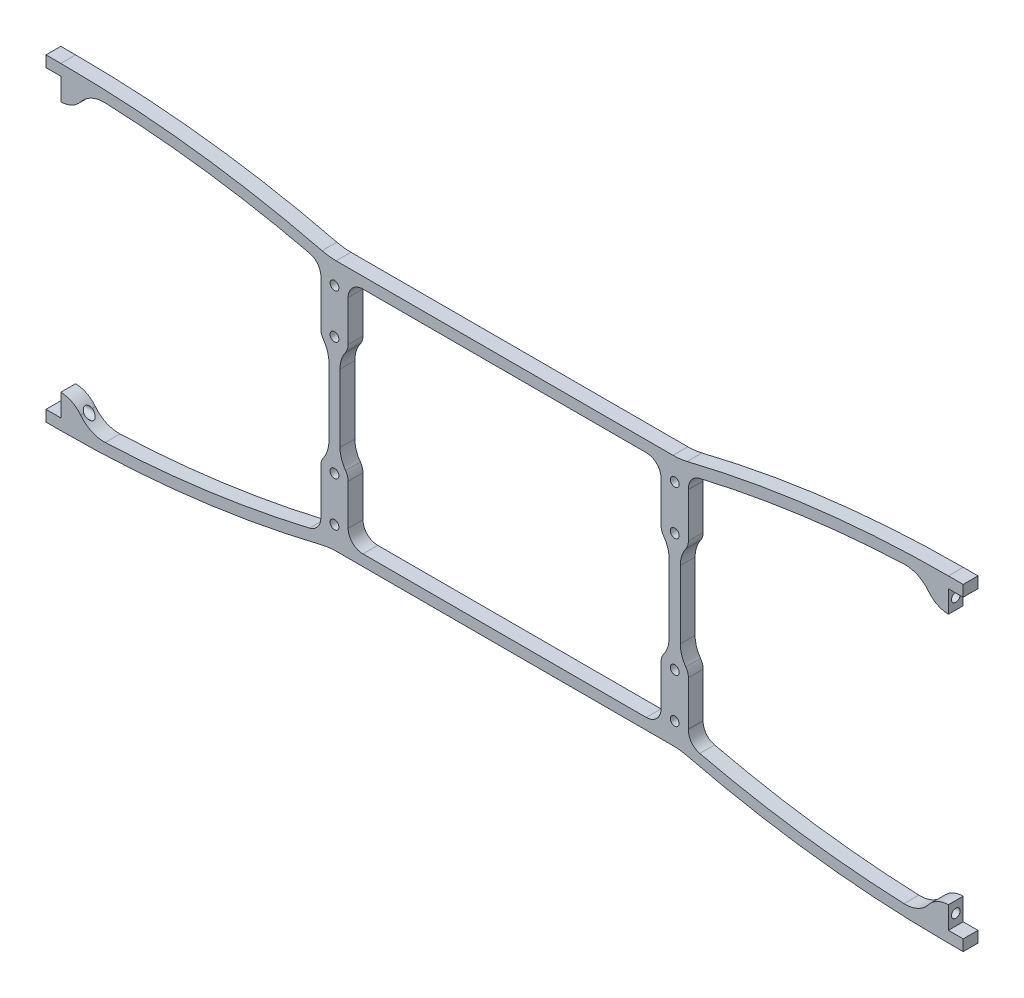
SolidWorks part; units mm, degrees
material "6061-T6 (SS)"
ref_plane "Front Plane" through (0, 0, 0) normal (0, 0, 1) x (1, 0, 0)
ref_plane "Top Plane" through (0, 0, 0) normal (0, 1, 0) x (1, 0, 0)
ref_plane "Right Plane" through (0, 0, 0) normal (1, 0, 0) x (0, 0, -1)
sketch "Sketch1" plane through (0, 0, 0) normal (0, 0, 1) x (1, 0, 0)
  line L0 (0, 49.2125) -> (0, -49.2125) construction
  line L2 (-70.6437, 0) -> (70.6437, 0) construction
  line L3 (70.6437, -49.2125) -> (-70.6437, -49.2125)
  line L4 (70.6437, -49.2125) -> (70.6437, 49.2125)
  line L5 (70.6437, 49.2125) -> (-70.6437, 49.2125)
  line L6 (-70.6437, -49.2125) -> (-70.6437, 49.2125)
  line L8 (-196.85, 65.8813) -> (-190.5, 65.8812) construction
  line L9 (-196.85, 68.2625) -> (-190.5, 68.2625)
  line L10 (75.4063, -53.975) -> (-75.4062, -53.975)
  line L11 (75.4063, -53.975) -> (75.4063, 53.975)
  line L12 (75.4063, 53.975) -> (-75.4062, 53.975)
  line L13 (-75.4062, -53.975) -> (-75.4062, 53.975)
  line L14 (-196.85, 63.5) -> (-190.5, 63.5)
  line L15 (-196.85, 63.5) -> (-196.85, 68.2625)
  line L16 (-190.5, 68.2625) -> (-190.5, 63.5)
  line L17 (-196.85, -65.8813) -> (-190.5, -65.8813) construction
  line L18 (-190.5, -68.2625) -> (-190.5, -63.5)
  line L19 (-196.85, -63.5) -> (-196.85, -68.2625)
  line L20 (-196.85, -63.5) -> (-190.5, -63.5)
  line L21 (-196.85, -68.2625) -> (-190.5, -68.2625)
  line L22 (196.85, -65.8812) -> (190.5, -65.8812) construction
  line L23 (196.85, 65.8813) -> (190.5, 65.8813) construction
  line L24 (196.85, -68.2625) -> (190.5, -68.2625)
  line L25 (196.85, -63.5) -> (190.5, -63.5)
  line L26 (196.85, -63.5) -> (196.85, -68.2625)
  line L27 (190.5, -68.2625) -> (190.5, -63.5)
  line L28 (190.5, 68.2625) -> (190.5, 63.5)
  line L29 (196.85, 63.5) -> (196.85, 68.2625)
  line L30 (196.85, 63.5) -> (190.5, 63.5)
  line L31 (196.85, 68.2625) -> (190.5, 68.2625)
  line L32 (-73.025, -53.975) -> (-73.025, 53.975) construction
  arc A0 (-27.6178, 36.6442) -> (-190.5, 65.8812) centre (-190.5, -402.4533) ccw construction
  arc A1 (-75.4062, 53.975) -> (-190.5, 68.2625) centre (-190.5, -402.4533) ccw
  arc A2 (-75.4062, 49.0618) -> (-190.5, 63.5) centre (-190.5, -402.4533) ccw
  arc A3 (34.7381, 10.8761) -> (-190.5, 68.2625) centre (-190.5, -402.4533) ccw construction
  arc A4 (32.4592, 6.6942) -> (-190.5, 63.5) centre (-190.5, -402.4533) ccw construction
  arc A5 (33.5986, 8.7851) -> (-190.5, 65.8812) centre (-190.5, -402.4533) ccw construction
  arc A6 (-75.4062, -49.0618) -> (-190.5, -63.5) centre (-190.5, 402.4533) cw
  arc A7 (-75.4062, -53.975) -> (-190.5, -68.2625) centre (-190.5, 402.4533) cw
  arc A8 (75.4062, -53.975) -> (190.5, -68.2625) centre (190.5, 402.4533) ccw
  arc A9 (75.4062, -49.0618) -> (190.5, -63.5) centre (190.5, 402.4533) ccw
  arc A10 (75.4062, 49.0618) -> (190.5, 63.5) centre (190.5, -402.4533) cw
  arc A11 (75.4062, 53.975) -> (190.5, 68.2625) centre (190.5, -402.4533) cw
  point P1 (0, 0)
  point P9 (0, 0)
  dimension "D1" = 4.7625
  dimension "D2" = 4.7625
  dimension "D5" = 6.35
  dimension "D3" = 107.95
  dimension "D7" = 131.7625
  dimension "D8" = 2.3813
  dimension "D6" = 381
  dimension "D4" = 146.05
  dimension "D10" = 0
  dimension "D9" = 2.3813
extrude "Boss-Extrude1" add sketch "Sketch1" along normal blind 6.35
sketch "Sketch2" plane through (0, 0, 6.35) normal (0, 0, 1) x (1, 0, 0)
  line L1 (-190.5, 65.8812) -> (-184.15, 65.8813)
  line L2 (-190.5, 65.8812) -> (-190.5, 53.975)
  line L3 (-190.5, 53.975) -> (-184.15, 53.975)
  line L4 (-184.15, 65.8813) -> (-184.15, 53.975)
  line L5 (0, 0) -> (0, 49.2125) construction
  line L7 (0, 0) -> (44.5192, 0) construction
  line L8 (-70.6437, 0) -> (70.6437, 0) construction
  line L9 (-190.5, -53.975) -> (-184.15, -53.975)
  line L10 (-190.5, -65.8812) -> (-184.15, -65.8813)
  line L11 (-190.5, -65.8812) -> (-190.5, -53.975)
  line L12 (-184.15, -65.8813) -> (-184.15, -53.975)
  line L13 (184.15, -65.8813) -> (184.15, -53.975)
  line L14 (190.5, -65.8812) -> (190.5, -53.975)
  line L15 (190.5, -65.8812) -> (184.15, -65.8813)
  line L16 (190.5, -53.975) -> (184.15, -53.975)
  line L17 (184.15, 65.8813) -> (184.15, 53.975)
  line L18 (190.5, 53.975) -> (184.15, 53.975)
  line L19 (190.5, 65.8812) -> (190.5, 53.975)
  line L20 (190.5, 65.8812) -> (184.15, 65.8813)
  line L21 (-196.85, 63.5) -> (-190.5, 63.5) construction
  dimension "D1" = 9.525
  dimension "D2" = 6.35
extrude "Boss-Extrude2" add sketch "Sketch2" against normal up to surface (6.35 mm away) contours L4 L1 L2 L3 | L10 L12 L9 L11 | L19 L20 L17 L18 | L14 L16 L13 L15 up to face at (0, 0, 0)
fillet "Fillet1" radius 12.7 4 edges at (184.15, 63.4567, 3.175) (184.15, -63.4567, 3.175) (-184.15, -63.4567, 3.175) (-184.15, 63.4567, 3.175)
fillet "Fillet2" radius 11.1125 4 edges at (184.15, 53.975, 3.175) (184.15, -53.975, 3.175) (-184.15, -53.975, 3.175) (-184.15, 53.975, 3.175)
hole_wizard "#6 Clearance Hole1" positions "Sketch4" profile "Sketch3" hole size "#6" standard "ANSI Inch" end condition through all
sketch "Sketch4" plane through (0, 0, 6.35) normal (0, 0, 1) x (1, 0, 0)
  line L0 (75.4063, 53.975) -> (-75.4062, 53.975) construction
  line L1 (0, 0) -> (0, 28.9554) construction
  line L4 (0, 0) -> (28.6284, 0) construction
  line L7 (-73.025, 53.975) -> (-73.025, 16.814) construction
  line L9 (-75.4062, -49.0618) -> (-75.4062, 49.0618) construction
  line L10 (-70.6437, -49.2125) -> (-70.6437, 49.2125) construction
  point P0 (-73.025, 44.45)
  point P2 (-73.025, 25.4)
  point P29 (73.025, 25.4)
  point P30 (73.025, 44.45)
  point P31 (73.025, -44.45)
  point P32 (73.025, -25.4)
  point P33 (-73.025, -25.4)
  point P34 (-73.025, -44.45)
  dimension "D1" = 9.525
  dimension "D2" = 28.575
sketch "Sketch3" plane through (-73.025, 44.45, 6.35) normal (1, 0, 0) x (0, -1, 0)
  line L0 (0, 0) -> (0, 6.35)
  line L1 (0, 6.35) -> (1.8986, 6.35)
  line L2 (1.8986, 6.35) -> (1.8986, 0)
  line L5 (1.8986, 0) -> (0, 0)
  line L11 (0, -6.35) -> (0, 107.95) construction
  dimension "Thru Hole Dia." = 3.7973
  dimension "Thru Hole Depth" = 6.35
sketch "Sketch5" plane through (0, 0, 6.35) normal (0, 0, 1) x (1, 0, 0)
  line L0 (0, 0) -> (0, 21.4363) construction
  line L1 (0, 0) -> (26.5768, 0) construction
  line L2 (-78.8924, 44.45) -> (-78.8924, 25.4)
  line L3 (-67.1576, 44.45) -> (-67.1576, 25.4)
  line L4 (67.1576, 44.45) -> (67.1576, 25.4)
  line L5 (78.8924, 44.45) -> (78.8924, 25.4)
  line L6 (-67.1576, 44.45) -> (-67.1576, 25.4)
  line L7 (78.8924, -44.45) -> (78.8924, -25.4)
  line L8 (67.1576, -44.45) -> (67.1576, -25.4)
  line L9 (-67.1576, -44.45) -> (-67.1576, -25.4)
  line L10 (-78.8924, -44.45) -> (-78.8924, -25.4)
  circle A0 centre (-73.025, 44.45) radius 5.8674
  circle A1 centre (-73.025, 25.4) radius 5.8674
  circle A2 centre (-73.025, 44.45) radius 1.8987 construction
  circle A3 centre (73.025, 25.4) radius 5.8674
  circle A4 centre (73.025, 44.45) radius 5.8674
  circle A5 centre (73.025, -25.4) radius 5.8674
  circle A6 centre (73.025, -44.45) radius 5.8674
  circle A7 centre (-73.025, -44.45) radius 5.8674
  circle A8 centre (-73.025, -25.4) radius 5.8674
  circle A9 centre (-73.025, 44.45) radius 1.8987
  circle A10 centre (-73.025, 25.4) radius 1.8987
  circle A11 centre (-73.025, 25.4) radius 1.8987 construction
  circle A12 centre (73.025, 25.4) radius 1.8987
  circle A13 centre (73.025, 44.45) radius 1.8987
  circle A14 centre (73.025, -44.45) radius 1.8987
  circle A15 centre (73.025, -25.4) radius 1.8987
  circle A16 centre (-73.025, -25.4) radius 1.8987
  circle A17 centre (-73.025, -44.45) radius 1.8987
  arc M46 (-171.438, 63.1099) -> (-75.4062, 49.0618) centre (-190.5, -402.4533) cw
  line M47 (-75.4062, 49.0618) -> (-75.4062, -49.0618)
  arc M48 (-75.4062, -49.0618) -> (-171.438, -63.1099) centre (-190.5, 402.4533) cw
  arc M64 (171.438, -63.1099) -> (75.4063, -49.0618) centre (190.5, 402.4533) cw
  line M65 (75.4063, -49.0618) -> (75.4063, 49.0618)
  arc M66 (75.4063, 49.0618) -> (171.438, 63.1099) centre (190.5, -402.4533) cw
  line M67 (70.6437, -49.2125) -> (-70.6437, -49.2125)
  line M68 (-70.6437, -49.2125) -> (-70.6437, 49.2125)
  line M69 (-70.6437, 49.2125) -> (70.6437, 49.2125)
  line M70 (70.6437, 49.2125) -> (70.6437, -49.2125)
  dimension "D1" = 7.766
extrude "Boss-Extrude3" add sketch "Sketch5" against normal through all contours A1 A0 L2 M47 | A0 M46 M47 | A0 M69 M68 | A1 L3 A0 M68 | A1 M68 | A1 M47 | A8 M47 | A8 L10 A7 M47 | A7 M48 M47 | L9 A8 A7 M68 | A8 M68 | A7 M68 M67 | A5 M70 | A6 A5 L8 M70 | A6 M70 M67 | A6 M65 M64 | A6 L7 A5 M65 | A5 M65 | L5 A4 A3 M65 | A4 M66 M65 | A4 M70 M69 | A4 L4 A3 M70 | A3 M70 | A3 M65
fillet "Fillet6" radius 6.35 8 edges at (76.3319, 49.2968, 3.175) (69.5979, 49.2125, 3.175) (76.3319, -49.2968, 3.175) (69.5979, -49.2125, 3.175) (-69.5979, -49.2125, 3.175) (-76.3319, -49.2968, 3.175) (-69.5979, 49.2125, 3.175) (-76.3319, 49.2968, 3.175)
fillet "Fillet7" radius 12.7 8 edges at (75.4063, 20.0375, 3.175) (70.6437, 20.0375, 3.175) (70.6437, -20.0375, 3.175) (75.4063, -20.0375, 3.175) (-75.4062, -20.0375, 3.175) (-70.6437, -20.0375, 3.175) (-70.6437, 20.0375, 3.175) (-75.4062, 20.0375, 3.175)
hole_wizard "Tap Drill for #6 Helicoil1" positions "Sketch7" profile "Sketch6" hole size "#6-32" standard "ANSI Inch"
sketch "Sketch7" plane through (190.5, 0, 0) normal (1, 0, 0) x (0, 0, -1)
  line L0 (-6.35, 58.7375) -> (0, 58.7375) construction
  line L1 (-6.35, 63.5) -> (-6.35, 53.975) construction
  line L2 (0, 53.975) -> (0, 63.5) construction
  line L5 (-3.175, 63.5) -> (-3.175, 53.975) construction
  line L6 (-6.35, 63.5) -> (0, 63.5) construction
  line L7 (0, 53.975) -> (-6.35, 53.975) construction
  line L8 (-3.175, -53.975) -> (-3.175, -63.5) construction
  line L9 (0, -53.975) -> (-6.35, -53.975) construction
  line L10 (-6.35, -63.5) -> (0, -63.5) construction
  line L13 (-6.35, -58.7375) -> (0, -58.7375) construction
  line L14 (-6.35, -63.5) -> (-6.35, -53.975) construction
  line L15 (0, -53.975) -> (0, -63.5) construction
  point P18 (-3.175, 58.7375)
  point P39 (-3.175, -58.7375)
sketch "Sketch6" plane through (190.5, 58.7375, 3.175) normal (0, 1, 0) x (0, 0, -1)
  line L0 (0, 0) -> (0, 94.2147)
  line L1 (0, 94.2147) -> (1.8669, 94.2147)
  line L2 (1.8669, 94.2147) -> (1.8669, 0)
  line L5 (1.8669, 0) -> (0, 0)
  line L11 (0, -6.35) -> (0, 107.95) construction
  dimension "Thru Hole Dia." = 3.7338
  dimension "Thru Hole Depth" = 94.2147
mirror "Mirror1" about plane through (0, 0, 0) normal (1, 0, 0) of "Tap Drill for #6 Helicoil1"
ref_plane "Plane1" through (0, 0, 0) normal (0, -0.866, -0.5) x (1, 0, 0)
fillet "Fillet8" radius 25.4 4 edges at (-75.4062, -53.975, 3.175) (75.4063, -53.975, 3.175) (75.4063, 53.975, 3.175) (-75.4062, 53.975, 3.175)
